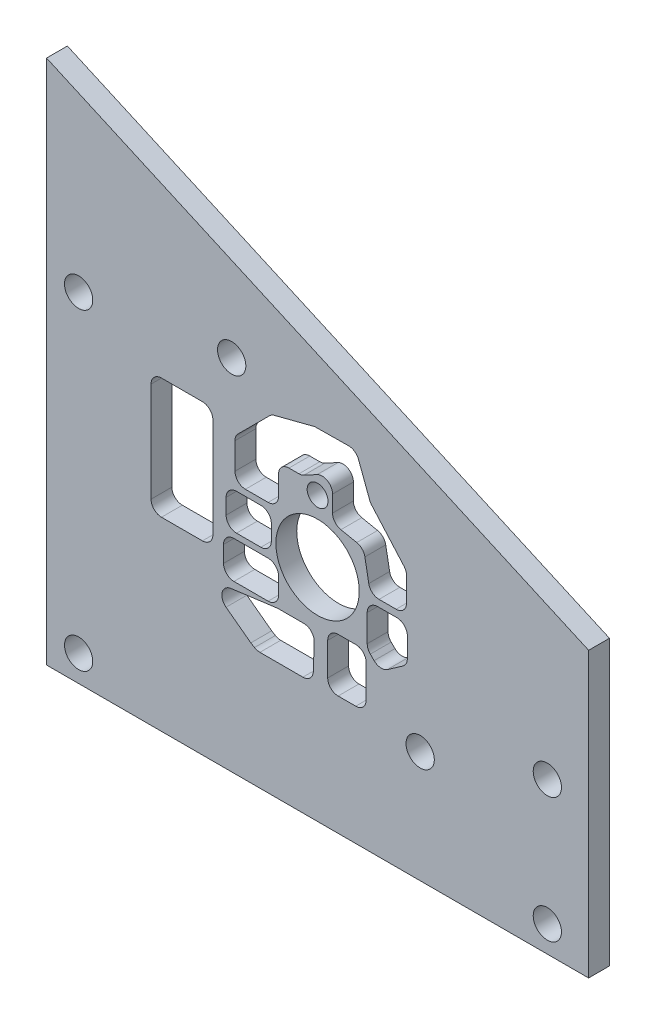
SolidWorks part; units mm, degrees
ref_plane "Front Plane" through (0, 0, 0) normal (0, 0, 1) x (1, 0, 0)
ref_plane "Top Plane" through (0, 0, 0) normal (0, 1, 0) x (1, 0, 0)
ref_plane "Right Plane" through (0, 0, 0) normal (1, 0, 0) x (0, 0, -1)
sketch "Sketch1" plane through (0, 0, 0) normal (0, 0, 1) x (1, 0, 0)
  line L16 (49.022, 13.462) -> (57.658, 13.462)
  line L17 (62.738, 8.382) -> (62.738, 0)
  line L18 (62.738, 0) -> (82.55, 0)
  line L19 (82.55, 0) -> (82.55, 58.42)
  line L20 (82.55, 58.42) -> (0, 95.25)
  line L21 (0, 95.25) -> (0, 0)
  line L22 (0, 0) -> (43.942, 0)
  line L23 (43.942, 0) -> (43.942, 8.382)
  arc A4 (62.738, 8.382) -> (57.658, 13.462) centre (57.658, 8.382) ccw
  arc A5 (49.022, 13.462) -> (43.942, 8.382) centre (49.022, 8.382) ccw
extrude "Boss-Extrude1" add sketch "Sketch1" against normal blind 3.175
hole_wizard "#6 Clearance Hole1" positions "Sketch3" profile "Sketch2" hole size "#6" standard "ANSI Inch" end condition through all
sketch "Sketch3" plane through (0, 0, -3.175) normal (0, 0, -1) x (-1, 0, 0)
  point P0 (-4.8895, 17.4625)
  point P4 (-4.8895, 65.0875)
  point P7 (-76.2635, 36.5125)
  point P10 (-76.2635, 17.4625)
  point P14 (-28.194, 68.072)
  point P17 (-56.896, 30.48)
sketch "Sketch2" plane through (4.8895, 17.4625, -3.175) normal (1, 0, 0) x (0, 1, 0)
  line L0 (0, 0) -> (0, 3.175)
  line L1 (0, 3.175) -> (2.1526, 3.175)
  line L2 (2.1526, 3.175) -> (2.1526, 0)
  line L5 (2.1526, 0) -> (0, 0)
  line L11 (0, -6.35) -> (0, 107.95) construction
  dimension "Thru Hole Dia." = 4.3053
  dimension "Thru Hole Depth" = 3.175
hole_wizard "1/2 (0.5) Diameter Hole1" positions "Sketch5" profile "Sketch4" hole size "1/2" standard "ANSI Inch" end condition through all
sketch "Sketch5" plane through (0, 0, -3.175) normal (0, 0, -1) x (-1, 0, 0)
  point P0 (-41.275, 46.99)
sketch "Sketch4" plane through (41.275, 46.99, -3.175) normal (1, 0, 0) x (0, 1, 0)
  line L0 (0, 0) -> (0, 3.175)
  line L1 (0, 3.175) -> (6.35, 3.175)
  line L2 (6.35, 3.175) -> (6.35, 0)
  line L5 (6.35, 0) -> (0, 0)
  line L11 (0, -6.35) -> (0, 107.95) construction
  dimension "Thru Hole Dia." = 12.7
  dimension "Thru Hole Depth" = 3.175
hole_wizard "1/8 (0.125) Diameter Hole1" positions "Sketch7" profile "Sketch6" hole size "1/8" standard "ANSI Inch" end condition through all
sketch "Sketch7" plane through (0, 0, 0) normal (0, 0, 1) x (1, 0, 0)
  point P0 (41.275, 56.4889)
sketch "Sketch6" plane through (41.275, 56.4889, 0) normal (1, 0, 0) x (0, -1, 0)
  line L0 (0, 0) -> (0, 3.175)
  line L1 (0, 3.175) -> (1.5875, 3.175)
  line L2 (1.5875, 3.175) -> (1.5875, 0)
  line L5 (1.5875, 0) -> (0, 0)
  line L11 (0, -6.35) -> (0, 107.95) construction
  dimension "Thru Hole Dia." = 3.175
  dimension "Thru Hole Depth" = 3.175
sketch "Sketch9" plane through (0, 0, 0) normal (0, 0, 1) x (1, 0, 0)
  line L1 (82.55, 58.42) -> (0, 95.25) construction
  line L2 (81.9032, 56.9702) -> (-0.6468, 93.8002)
  line L3 (82.55, 56.6817) -> (0, 93.5117)
  line L4 (82.55, 58.42) -> (0, 95.25)
  line L5 (82.55, 0) -> (82.55, 58.42) construction
  line L6 (0, 95.25) -> (0, 0) construction
  line L7 (0, 95.25) -> (0, 93.5117)
  line L8 (82.55, 58.42) -> (82.55, 56.6817)
  dimension "D1" = 1.5875
extrude "Cut-Extrude1" cut sketch "Sketch9" against normal through all
sketch "Sketch10" plane through (0, 0, 0) normal (0, 0, 1) x (1, 0, 0)
  line L0 (0, 93.5117) -> (0, 0) construction
  line L1 (82.55, 0) -> (0, 0)
  line L2 (82.55, 0) -> (82.55, 13.462)
  line L3 (82.55, 13.462) -> (0, 13.462)
  line L4 (0, 0) -> (0, 13.462)
  line L5 (49.022, 13.462) -> (57.658, 13.462) construction
extrude "Cut-Extrude2" cut sketch "Sketch10" against normal through all
sketch "Sketch11" plane through (0, 0, -3.175) normal (0, 0, -1) x (-1, 0, 0)
  line L0 (-47.4994, 64.35) -> (-49.2178, 59.797)
  line L1 (-49.5116, 59.3085) -> (-54.4247, 53.7282)
  line L2 (-54.8207, 52.6791) -> (-54.8207, 49.0282)
  line L3 (-53.2332, 47.4407) -> (-50.632, 47.4407)
  line L4 (-49.0704, 48.7427) -> (-48.481, 51.9664)
  line L5 (-47.2367, 53.2364) -> (-44.8263, 53.7281)
  line L6 (-43.556, 55.2835) -> (-43.556, 57.7887)
  line L10 (-35.3315, 56.3146) -> (-35.3315, 53.3713)
  line L11 (-33.744, 51.7838) -> (-30.2845, 51.7838)
  line L12 (-28.697, 53.3713) -> (-28.697, 57.3946)
  line L13 (-29.1619, 58.5172) -> (-33.9603, 63.3155)
  line L14 (-34.685, 63.7298) -> (-40.6377, 65.2708)
  line L15 (-45.9965, 65.3769) -> (-41.0178, 65.3214)
  line L17 (-41.2134, 59.1851) -> (-39.1943, 58.0932)
  line L18 (-38.4391, 57.9021) -> (-36.919, 57.9021)
  line L19 (-32.6464, 50.8408) -> (-28.9301, 50.8408)
  line L20 (-34.2339, 49.2533) -> (-34.2339, 46.9055)
  line L21 (-32.6464, 45.318) -> (-28.9301, 45.318)
  line L22 (-27.3426, 46.9055) -> (-27.3426, 49.2533)
  line L23 (-35.3315, 42.8403) -> (-35.3315, 40.3434)
  line L24 (-33.744, 38.7559) -> (-28.5401, 38.7559)
  line L25 (-26.9526, 40.3434) -> (-26.9526, 42.8403)
  line L26 (-28.5401, 44.4278) -> (-33.744, 44.4278)
  line L27 (-39.176, 38.541) -> (-35.2855, 38.541)
  line L29 (-31.1146, 31.9414) -> (-31.6722, 31.6068)
  line L30 (-32.489, 31.3805) -> (-39.0389, 31.3805)
  line L31 (-40.6255, 32.9134) -> (-40.7626, 36.8989)
  line L32 (-42.8176, 33.1652) -> (-42.8176, 38.125)
  line L33 (-44.4051, 39.7125) -> (-47.0833, 39.7125)
  line L34 (-48.6708, 38.125) -> (-48.6708, 33.1652)
  line L35 (-47.0833, 31.5777) -> (-44.4051, 31.5777)
  line L36 (-49.8872, 38.9868) -> (-49.3079, 39.5556)
  line L37 (-48.8326, 40.6883) -> (-48.8326, 44.7971)
  line L38 (-50.4201, 46.3846) -> (-53.3578, 46.3846)
  line L39 (-54.9453, 44.7971) -> (-54.9453, 41.7679)
  line L40 (-54.2673, 40.4668) -> (-51.909, 38.8183)
  line L41 (-31.1146, 31.9414) -> (-27.3347, 34.7543)
  line L42 (-28.0744, 37.6016) -> (-35.0774, 38.5273)
  line L43 (-25.3285, 58.4747) -> (-25.3285, 43.2937)
  line L44 (-23.741, 41.7062) -> (-17.5042, 41.7062)
  line L45 (-15.9167, 43.2937) -> (-15.9167, 58.4747)
  line L46 (-17.5042, 60.0622) -> (-23.741, 60.0622)
  arc A0 (-28.697, 57.3946) -> (-29.1619, 58.5172) centre (-30.2845, 57.3946) ccw
  arc A1 (-30.2845, 51.7838) -> (-28.697, 53.3713) centre (-30.2845, 53.3713) ccw
  arc A2 (-35.3315, 53.3713) -> (-33.744, 51.7838) centre (-33.744, 53.3713) ccw
  arc A4 (-33.9603, 63.3155) -> (-34.685, 63.7298) centre (-35.0828, 62.193) ccw
  arc A5 (-47.4994, 64.35) -> (-45.9965, 65.3769) centre (-46.0142, 63.7895) cw
  arc A6 (-49.2178, 59.797) -> (-49.5116, 59.3085) centre (-50.7031, 60.3576) cw
  arc A7 (-54.4247, 53.7282) -> (-54.8207, 52.6791) centre (-53.2332, 52.6791) ccw
  arc A8 (-54.8207, 49.0282) -> (-53.2332, 47.4407) centre (-53.2332, 49.0282) ccw
  arc A9 (-50.632, 47.4407) -> (-49.0704, 48.7427) centre (-50.632, 49.0282) ccw
  arc A10 (-48.481, 51.9664) -> (-47.2367, 53.2364) centre (-46.9194, 51.6809) cw
  arc A11 (-44.8263, 53.7281) -> (-43.556, 55.2835) centre (-45.1435, 55.2835) ccw
  arc A13 (-40.6377, 65.2708) -> (-41.0178, 65.3214) centre (-41.0355, 63.734) ccw
  arc A14 (-36.919, 57.9021) -> (-35.3315, 56.3146) centre (-36.919, 56.3146) cw
  arc A15 (-39.1943, 58.0932) -> (-38.4391, 57.9021) centre (-38.4391, 59.4896) ccw
  arc A16 (-43.556, 57.7887) -> (-41.2134, 59.1851) centre (-41.9685, 57.7887) cw
  arc A17 (-28.9301, 50.8408) -> (-27.3426, 49.2533) centre (-28.9301, 49.2533) cw
  arc A18 (-28.9301, 45.318) -> (-27.3426, 46.9055) centre (-28.9301, 46.9055) ccw
  arc A19 (-34.2339, 46.9055) -> (-32.6464, 45.318) centre (-32.6464, 46.9055) ccw
  arc A20 (-32.6464, 50.8408) -> (-34.2339, 49.2533) centre (-32.6464, 49.2533) ccw
  arc A21 (-26.9526, 42.8403) -> (-28.5401, 44.4278) centre (-28.5401, 42.8403) ccw
  arc A22 (-28.5401, 38.7559) -> (-26.9526, 40.3434) centre (-28.5401, 40.3434) ccw
  arc A23 (-35.3315, 40.3434) -> (-33.744, 38.7559) centre (-33.744, 40.3434) ccw
  arc A24 (-35.3315, 42.8403) -> (-33.744, 44.4278) centre (-33.744, 42.8403) cw
  arc A25 (-39.0389, 31.3805) -> (-40.6255, 32.9134) centre (-39.0389, 32.968) cw
  arc A26 (-31.6722, 31.6068) -> (-32.489, 31.3805) centre (-32.489, 32.968) cw
  arc A29 (-39.176, 38.541) -> (-40.7626, 36.8989) centre (-39.176, 36.9535) ccw
  arc A30 (-48.6708, 33.1652) -> (-47.0833, 31.5777) centre (-47.0833, 33.1652) ccw
  arc A31 (-47.0833, 39.7125) -> (-48.6708, 38.125) centre (-47.0833, 38.125) ccw
  arc A32 (-42.8176, 38.125) -> (-44.4051, 39.7125) centre (-44.4051, 38.125) ccw
  arc A33 (-42.8176, 33.1652) -> (-44.4051, 31.5777) centre (-44.4051, 33.1652) cw
  arc A34 (-48.8326, 44.7971) -> (-50.4201, 46.3846) centre (-50.4201, 44.7971) ccw
  arc A35 (-49.3079, 39.5556) -> (-48.8326, 40.6883) centre (-50.4201, 40.6883) ccw
  arc A36 (-49.8872, 38.9868) -> (-51.909, 38.8183) centre (-50.9995, 40.1195) cw
  arc A37 (-54.9453, 41.7679) -> (-54.2673, 40.4668) centre (-53.3578, 41.7679) ccw
  arc A38 (-53.3578, 46.3846) -> (-54.9453, 44.7971) centre (-53.3578, 44.7971) ccw
  arc A39 (-27.3347, 34.7543) -> (-28.0744, 37.6016) centre (-28.2825, 36.0278) ccw
  arc A40 (-35.2855, 38.541) -> (-35.0774, 38.5273) centre (-35.2855, 36.9535) cw
  arc A41 (-17.5042, 41.7062) -> (-15.9167, 43.2937) centre (-17.5042, 43.2937) ccw
  arc A42 (-25.3285, 43.2937) -> (-23.741, 41.7062) centre (-23.741, 43.2937) ccw
  arc A43 (-25.3285, 58.4747) -> (-23.741, 60.0622) centre (-23.741, 58.4747) cw
  arc A44 (-15.9167, 58.4747) -> (-17.5042, 60.0622) centre (-17.5042, 58.4747) ccw
  dimension "D1" = 1.5875
  dimension "D2" = 1.5875
  dimension "D3" = 1.5875
  dimension "D4" = 1.5875
  dimension "D5" = 1.5875
  dimension "D6" = 1.5875
  dimension "D7" = 1.5875
  dimension "D8" = 1.5875
  dimension "D9" = 1.5875
  dimension "D10" = 1.5875
  dimension "D11" = 1.5875
extrude "Cut-Extrude3" cut sketch "Sketch11" against normal through all
